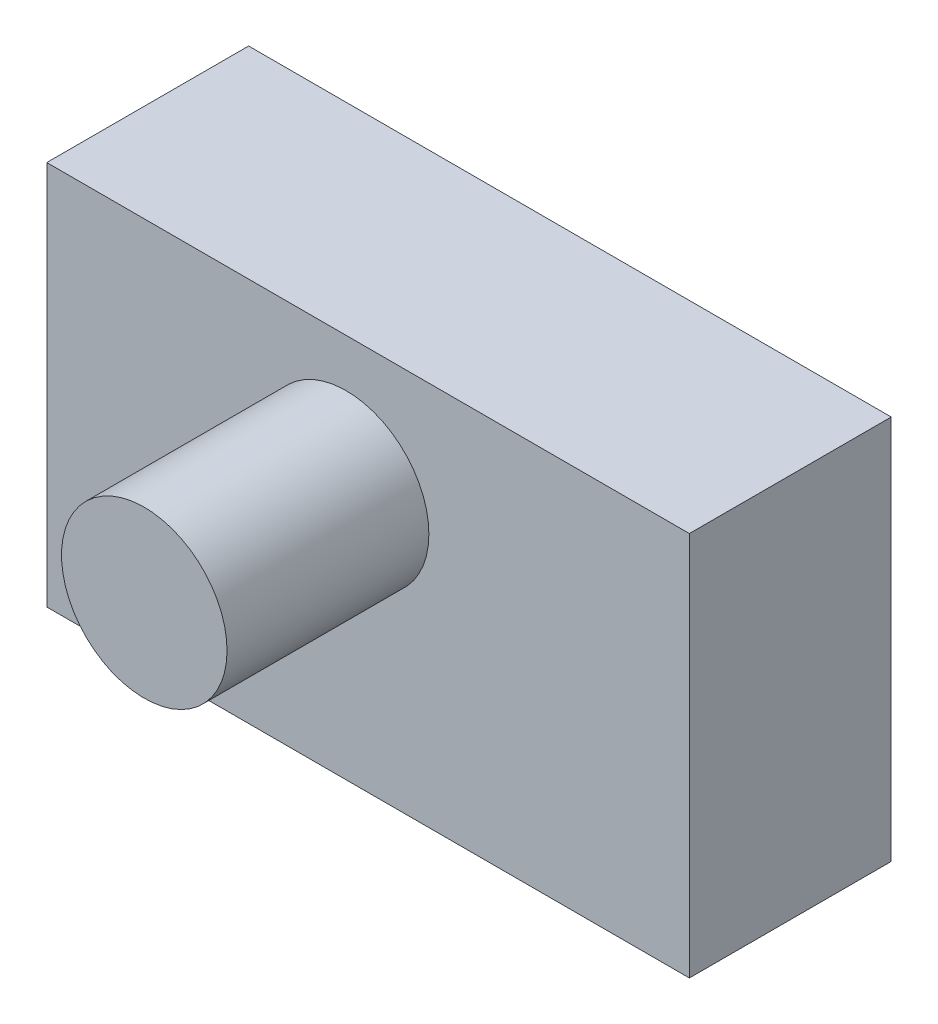
SolidWorks part; units mm, degrees
material "Al-Aly 7075-T7351 Plate per AMS 4078"
ref_plane "Z Plane" through (0, 0, 0) normal (0, 0, 1) x (1, 0, 0)
ref_plane "Y Plane" through (0, 0, 0) normal (0, 1, 0) x (1, 0, 0)
ref_plane "X Plane" through (0, 0, 0) normal (1, 0, 0) x (0, 0, -1)
ref_axis "X Axis" through (-88.99, 0, 0) along (1, 0, 0)
ref_axis "Z Axis" through (0, 0, -88.99) along (0, 0, 1)
ref_axis "Y Axis" through (0, 55, 0) along (0, -1, 0)
sketch "Sketch1" plane through (0, 0, 0) normal (0, 0, 1) x (1, 0, 0)
  line L1 (-80.8622, -48.4364) -> (80.8622, -48.4364)
  line L2 (-80.8622, -48.4364) -> (-80.8622, 48.4364)
  line L3 (-80.8622, 48.4364) -> (80.8622, 48.4364)
  line L4 (80.8622, -48.4364) -> (80.8622, 48.4364)
  line L5 (-80.8622, -48.4364) -> (80.8622, 48.4364) construction
  line L6 (-80.8622, 48.4364) -> (80.8622, -48.4364) construction
  point P0 (0, 0)
extrude "Boss-Extrude1" add sketch "Sketch1" along normal blind 50.8
sketch "Sketch2" plane through (0, 0, 50.8) normal (0, 0, 1) x (1, 0, 0)
  circle A0 centre (-5.5257, 15.5605) radius 20.831
extrude "Boss-Extrude2" add sketch "Sketch2" along normal blind 50.8 contours A0
